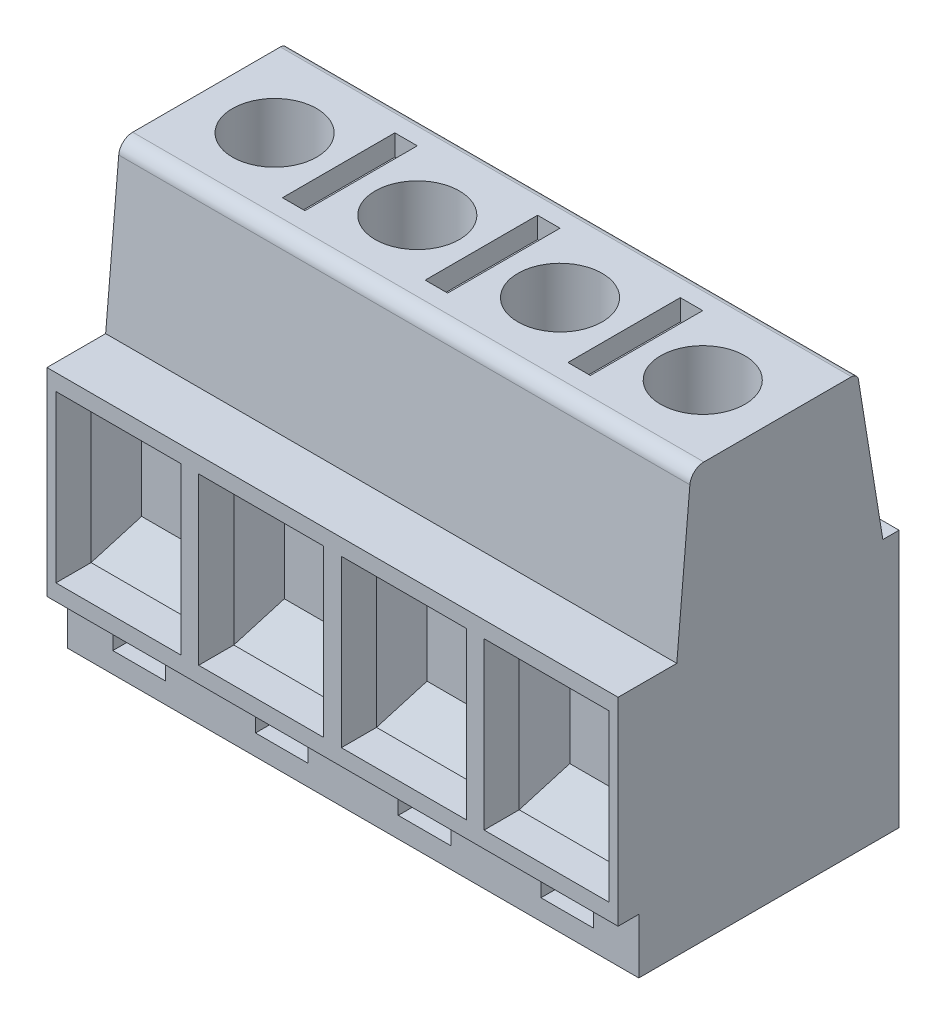
SolidWorks part; units mm, degrees
ref_plane "Front Plane" through (0, 0, 0) normal (0, 0, 1) x (1, 0, 0)
ref_plane "Top Plane" through (0, 0, 0) normal (0, 1, 0) x (1, 0, 0)
ref_plane "Right Plane" through (0, 0, 0) normal (1, 0, 0) x (0, 0, -1)
sketch "Sketch1" plane through (0, 0, 0) normal (1, 0, 0) x (0, 0, -1)
  line L0 (9.6447, 33.3244) -> (29.6447, 33.3244) construction
  line L1 (9.6692, 32.9692) -> (9.6692, 47.0868)
  line L2 (9.6692, 47.0868) -> (13.8475, 47.0868)
  line L3 (13.8475, 47.0868) -> (14.8593, 58.5419)
  line L4 (14.8593, 58.5419) -> (26.709, 58.5419)
  line L5 (26.709, 58.5419) -> (28.5149, 47.3865)
  line L6 (28.5149, 47.3865) -> (29.6692, 47.3865)
  line L7 (29.6692, 47.3865) -> (29.6692, 29.0419)
  line L8 (29.6692, 29.0419) -> (11.1423, 29.0419)
  line L9 (11.1423, 29.0419) -> (11.1423, 32.9692)
  line L10 (11.1423, 32.9692) -> (9.6692, 32.9692)
  line L11 (68.0457, 60.9618) -> (149.3457, 60.9618) construction
  line L12 (139.8559, 49.112) -> (148.7559, 49.112) construction
  line L13 (139.8559, 49.112) -> (139.8559, 37.312) construction
  line L14 (204.1416, 49.112) -> (206.6416, 49.112) construction
  line L15 (208.5587, 45.7504) -> (208.5587, 39.4578) construction
  line L16 (208.5587, 42.6041) -> (206.6416, 42.6041) construction
  line L17 (121.2763, 41.7533) -> (126.7736, 41.7533) construction
  line L18 (217.6919, 61.8593) -> (217.6919, 56.1569) construction
  line L19 (142.8406, 99.3741) -> (145.9297, 99.3741) construction
  line L20 (211.5813, 61.8593) -> (211.5813, 60.3558) construction
  line L21 (118.1896, 87.8673) -> (119.7969, 87.8673) construction
  line L22 (118.1896, 87.8673) -> (118.1896, 95.8627) construction
  line L23 (118.1896, 95.8627) -> (119.7969, 95.8627) construction
  line L24 (119.7969, 87.8673) -> (119.7969, 95.8627) construction
  line L25 (170.4098, 32.3653) -> (173.8098, 32.3653) construction
  line L26 (173.8098, 32.3653) -> (175.1098, 32.3653) construction
  line L27 (175.1098, 32.3653) -> (178.3098, 32.3653) construction
  line L28 (178.3098, 32.3653) -> (179.6098, 32.3653) construction
  line L29 (179.6098, 32.3653) -> (183.0098, 32.3653) construction
  line L30 (183.0098, 32.3653) -> (184.3098, 32.3653) construction
  line L31 (142.4541, 34.5696) -> (146.1866, 34.5696) construction
  line L32 (146.1866, 34.5696) -> (142.4541, 34.5696) construction
  line L33 (142.4541, 34.5696) -> (142.4541, 33.584) construction
  circle A0 centre (134.2519, 91.3377) radius 3.0186 construction
  dimension "D1" = 20
  dimension "D2" = 20
  dimension "D3" = 29.5
  dimension "D4" = 9.6692
  dimension "D5" = 11.1423
  dimension "D6" = 13.8475
  dimension "D7" = 14.8593
  dimension "D8" = 26.709
  dimension "D9" = 28.5149
  dimension "D10" = 29.0419
  dimension "D11" = 32.9692
  dimension "D12" = 33.3244
  dimension "D13" = 47.0868
  dimension "D14" = 47.3865
  dimension "D15" = 81.3
  dimension "D16" = 8.9
  dimension "D17" = 11.8
  dimension "D18" = 2.5
  dimension "D19" = 1.6073
  dimension "D20" = 7.9954
  dimension "D21" = 3.4
  dimension "D22" = 1.3
  dimension "D23" = 3.2
  dimension "D24" = 1.3
  dimension "D25" = 3.4
  dimension "D26" = 1.3
extrude "Boss-Extrude1" add sketch "Sketch1" along normal blind 10.16
sketch "Sketch2" plane through (0, 0, -9.6692) normal (0, 0, 1) x (1, 0, 0)
  line L0 (0, 47.0868) -> (0, 32.9692) construction
  line L1 (0.63, 34.128) -> (9.53, 34.128)
  line L2 (0.63, 34.128) -> (0.63, 45.928)
  line L3 (0.63, 45.928) -> (9.53, 45.928)
  line L4 (9.53, 34.128) -> (9.53, 45.928)
  line L5 (0.63, 34.128) -> (9.53, 45.928) construction
  line L6 (0.63, 45.928) -> (9.53, 34.128) construction
  line L7 (10.16, 47.0868) -> (0, 47.0868) construction
  point P0 (5.08, 40.028)
  point P5 (0, 0)
  point P8 (0, 40.028)
  point P9 (0, 0)
  point P12 (5.08, 47.0868)
  point P13 (9.3089, 45.6013)
  dimension "D1" = 8.9
  dimension "D2" = 11.8
extrude "Cut-Extrude1" cut sketch "Sketch2" against normal blind 2.5
sketch "Sketch3" plane through (0, 0, -12.1692) normal (0, 0, 1) x (1, 0, 0)
  line L4 (9.53, 34.128) -> (9.53, 45.928)
  line L5 (9.53, 45.928) -> (0.63, 45.928)
  line L6 (0.63, 45.928) -> (0.63, 34.128)
  line L7 (0.63, 34.128) -> (9.53, 34.128)
  line L8 (9.53, 34.128) -> (9.53, 45.928)
  line L9 (9.53, 45.928) -> (0.63, 45.928)
  line L10 (0.63, 45.928) -> (0.63, 34.128)
  line L11 (0.63, 34.128) -> (9.53, 34.128)
  dimension "D1" = 0
ref_plane "Plane1" through (0, 0, -14.0692) normal (0, 0, 1) x (1, 0, 0)
sketch "Sketch4" plane through (0, 0, -14.0692) normal (0, 0, 1) x (1, 0, 0)
  line L0 (9.53, 45.928) -> (0.63, 45.928) construction
  line L1 (2.33, 36.878) -> (7.83, 36.878)
  line L2 (2.33, 36.878) -> (2.33, 43.178)
  line L3 (2.33, 43.178) -> (7.83, 43.178)
  line L4 (7.83, 36.878) -> (7.83, 43.178)
  line L5 (2.33, 36.878) -> (7.83, 43.178) construction
  line L6 (2.33, 43.178) -> (7.83, 36.878) construction
  line L7 (0.63, 45.928) -> (0.63, 34.128) construction
  point P0 (5.08, 40.028)
  point P5 (0, 0)
  point P8 (5.08, 45.928)
  point P9 (0, 0)
  point P12 (0.63, 40.028)
  dimension "D1" = 6.3
  dimension "D2" = 5.5
loft "Cut-Loft1" cut profiles "Sketch3", "Sketch4" connector at (0.63, 45.928, -12.1692) connector at (2.33, 43.178, -14.0692)
sketch "Sketch5" plane through (0, 58.5419, 0) normal (0, 1, 0) x (1, 0, 0)
  line L0 (10.16, 26.709) -> (10.16, 14.8593) construction
  line L1 (10.16, 29.6692) -> (0, 29.6692) construction
  circle A0 centre (5.08, 20.7842) radius 3
  point P2 (0, 0)
  point P5 (10.16, 20.7842)
  point P6 (0, 0)
  point P9 (5.08, 29.6692)
  dimension "D1" = 6
extrude "Cut-Extrude2" cut sketch "Sketch5" against normal blind 5.7
sketch "Sketch7" plane through (0, 29.0419, 0) normal (0, -1, 0) x (1, 0, 0)
  line L0 (10.16, -11.1423) -> (0, -11.1423) construction
  line L1 (4.43, -27.5692) -> (5.73, -27.5692)
  line L2 (4.43, -27.5692) -> (4.43, -26.7692)
  line L3 (4.43, -26.7692) -> (5.73, -26.7692)
  line L4 (5.73, -27.5692) -> (5.73, -26.7692)
  line L5 (4.43, -27.5692) -> (5.73, -26.7692) construction
  line L6 (4.43, -26.7692) -> (5.73, -27.5692) construction
  line L7 (4.43, -17.4092) -> (5.73, -17.4092)
  line L8 (4.43, -17.4092) -> (4.43, -16.6092)
  line L9 (4.43, -16.6092) -> (5.73, -16.6092)
  line L10 (5.73, -17.4092) -> (5.73, -16.6092)
  line L11 (4.43, -17.4092) -> (5.73, -16.6092) construction
  line L12 (4.43, -16.6092) -> (5.73, -17.4092) construction
  line L13 (10.16, -29.6692) -> (0, -29.6692) construction
  point P0 (5.08, -27.1692)
  point P5 (5.08, -17.0092)
  point P10 (0, 0)
  point P13 (5.08, -11.1423)
  dimension "D1" = 1.3
  dimension "D2" = 0.8
  dimension "D3" = 2.5
  dimension "D4" = 10.16
extrude "Boss-Extrude2" add sketch "Sketch7" along normal blind 4.5
sketch "Sketch8" plane through (0, 0, -16.6092) normal (0, 0, 1) x (1, 0, 0)
  line L0 (4.43, 24.5419) -> (4.43, 29.0419) construction
  line L1 (5.73, 24.5419) -> (5.73, 29.0419) construction
  line L2 (5.73, 24.5419) -> (4.43, 24.5419) construction
  arc A0 (4.43, 25.1919) -> (5.73, 25.1919) centre (5.08, 25.1919) ccw
  point P3 (5.08, 24.5419)
extrude "Cut-Extrude5" cut sketch "Sketch8" against normal through all flip side to cut
ref_plane "Plane2" through (0, 38.5279, -38.5279) normal (0, 0.7071, -0.7071) x (-1, 0, 0)
sketch "Sketch10" plane through (0, 38.5279, -38.5279) normal (0, 0.7071, -0.7071) x (-1, 0, 0)
  line L0 (-10.16, 12.528) -> (0, 12.528) construction
  circle A0 centre (-5.08, 12.528) radius 1.5
  dimension "D1" = 3
extrude "Cut-Extrude6" cut sketch "Sketch10" against normal blind 4.5 contours A0
sketch "Sketch13" plane through (0, 0, -11.1423) normal (0, 0, 1) x (1, 0, 0)
  line L0 (10.16, 32.9692) -> (10.16, 29.0419) construction
  line L1 (3.205, 30.5055) -> (6.955, 30.5055)
  line L2 (3.205, 30.5055) -> (3.205, 31.5055)
  line L3 (3.205, 31.5055) -> (6.955, 31.5055)
  line L4 (6.955, 30.5055) -> (6.955, 31.5055)
  line L5 (3.205, 30.5055) -> (6.955, 31.5055) construction
  line L6 (3.205, 31.5055) -> (6.955, 30.5055) construction
  line L7 (10.16, 32.9692) -> (0, 32.9692) construction
  point P0 (5.08, 31.0055)
  point P5 (0, 0)
  point P8 (10.16, 31.0055)
  point P9 (0, 0)
  point P12 (5.08, 32.9692)
  dimension "D1" = 3.75
  dimension "D2" = 1
extrude "Cut-Extrude8" cut sketch "Sketch13" against normal blind 3
fillet "Fillet3" radius 0.5 1 edges at (5.08, 58.5419, -26.709) type face fillet first side face at (5.08, 58.5419, -17.7842) second side face at (5.08, 51.2437, -27.8905)
fillet "Fillet4" radius 1 1 edges at (5.08, 58.5419, -14.8593) type face fillet first side face at (5.08, 58.5419, -17.7842) second side face at (5.08, 52.8143, -14.3534)
sketch "Sketch12" plane through (0, 29.0419, 0) normal (0, -1, 0) x (1, 0, 0)
  line L1 (-0.65, -15.8423) -> (0.65, -15.8423)
  line L2 (-0.65, -15.8423) -> (-0.65, -14.5423)
  line L3 (-0.65, -14.5423) -> (0.65, -14.5423)
  line L4 (0.65, -15.8423) -> (0.65, -14.5423)
  line L5 (-0.65, -15.8423) -> (0.65, -14.5423) construction
  line L6 (-0.65, -14.5423) -> (0.65, -15.8423) construction
  line L8 (-0.65, -20.3423) -> (0.65, -20.3423)
  line L9 (-0.65, -20.3423) -> (-0.65, -19.0423)
  line L10 (-0.65, -19.0423) -> (0.65, -19.0423)
  line L11 (0.65, -20.3423) -> (0.65, -19.0423)
  line L12 (-0.65, -20.3423) -> (0.65, -19.0423) construction
  line L13 (-0.65, -19.0423) -> (0.65, -20.3423) construction
  line L14 (-0.65, -25.0423) -> (0.65, -25.0423)
  line L15 (-0.65, -25.0423) -> (-0.65, -23.7423)
  line L16 (-0.65, -23.7423) -> (0.65, -23.7423)
  line L17 (0.65, -25.0423) -> (0.65, -23.7423)
  line L18 (-0.65, -25.0423) -> (0.65, -23.7423) construction
  line L19 (-0.65, -23.7423) -> (0.65, -25.0423) construction
  line L20 (10.16, -11.1423) -> (0, -11.1423) construction
  line L21 (0, -11.1423) -> (0, -29.6692) construction
  point P0 (0, -15.1923)
  point P5 (0, 0)
  point P6 (0, -15.1923)
  point P7 (0, -19.6923)
  point P12 (0, -24.3923)
  point P21 (0, 0)
  point P22 (0, 0)
  point P23 (0, -15.1923)
  point P24 (0, -19.6923)
  point P25 (0, -24.3923)
  dimension "D1" = 3.4
  dimension "D2" = 1.3
  dimension "D3" = 3.2
  dimension "D4" = 3.4
  dimension "D5" = 1.3
extrude "Boss-Extrude3" add sketch "Sketch12" along normal blind 0.5 separate body
sketch "Sketch14" plane through (10.16, 0, 0) normal (1, 0, 0) x (0, 0, -1)
  line L10 (26.2835, 58.5419) -> (15.7749, 58.5419)
  line L11 (14.7788, 57.6298) -> (13.8475, 47.0868)
  line L12 (13.8475, 47.0868) -> (9.6692, 47.0868)
  line L13 (9.6692, 47.0868) -> (9.6692, 32.9692)
  line L14 (9.6692, 32.9692) -> (11.1423, 32.9692)
  line L15 (11.1423, 32.9692) -> (11.1423, 29.0419)
  line L16 (11.1423, 29.0419) -> (29.6692, 29.0419)
  line L17 (29.6692, 29.0419) -> (29.6692, 47.3865)
  line L18 (29.6692, 47.3865) -> (28.5149, 47.3865)
  line L19 (28.5149, 47.3865) -> (26.777, 58.1218)
  line L21 (14.7788, 57.6298) -> (13.8475, 47.0868)
  line L22 (13.8475, 47.0868) -> (9.6692, 47.0868)
  line L23 (9.6692, 47.0868) -> (9.6692, 32.9692)
  line L24 (9.6692, 32.9692) -> (11.1423, 32.9692)
  line L25 (11.1423, 32.9692) -> (11.1423, 29.0419)
  line L26 (11.1423, 29.0419) -> (29.6692, 29.0419)
  line L27 (29.6692, 29.0419) -> (29.6692, 47.3865)
  line L28 (29.6692, 47.3865) -> (28.5149, 47.3865)
  line L29 (28.5149, 47.3865) -> (26.777, 58.1218)
  line L31 (26.2835, 58.5419) -> (15.7749, 58.5419)
  arc A3 (26.777, 58.1218) -> (26.2835, 58.5419) centre (26.2835, 58.0419) ccw
  arc A6 (26.777, 58.1218) -> (26.2835, 58.5419) centre (26.2835, 58.0419) ccw
  arc A8 (15.7749, 58.5419) -> (14.7788, 57.6298) centre (15.7749, 57.5419) ccw
  arc A9 (15.7749, 58.5419) -> (14.7788, 57.6298) centre (15.7749, 57.5419) ccw
  dimension "D1" = 0
extrude "Boss-Extrude4" add sketch "Sketch14" along normal blind 0.01
ref_plane "Plane3" through (0, 0, 0) normal (-1, 0, 0) x (0, 0, 1)
pattern_linear "LPattern8" count 4 spacing 10.16 along (-1, 0, 0) of "Boss-Extrude1", "Cut-Extrude1", "Cut-Loft1", "Cut-Extrude2", "Boss-Extrude2", "Cut-Extrude5", "Cut-Extrude6", "Cut-Extrude8", "Fillet3", "Fillet4"
sketch "Sketch11" plane through (0, 58.5419, 0) normal (0, 1, 0) x (1, 0, 0)
  line L1 (-0.8, 17.0641) -> (0.8, 17.0641)
  line L2 (-0.8, 17.0641) -> (-0.8, 25.0641)
  line L3 (-0.8, 25.0641) -> (0.8, 25.0641)
  line L4 (0.8, 17.0641) -> (0.8, 25.0641)
  line L5 (-0.8, 17.0641) -> (0.8, 25.0641) construction
  line L6 (-0.8, 25.0641) -> (0.8, 17.0641) construction
  line L8 (0, 55) -> (0, -55) construction
  point P0 (0, 21.0641)
  point P5 (1.8522, 20.6032)
  point P6 (1.6707, 20.773)
  point P7 (0, 0)
  point P8 (0, 0)
  point P12 (0, 0)
  point P13 (0.3317, 21.0641)
  point P16 (0, 0)
  dimension "D1" = 1.6
  dimension "D2" = 8
extrude "Cut-Extrude7" cut sketch "Sketch11" against normal blind 1.5
pattern_linear "LPattern9" count 3 spacing 10.16 along (-1, 0, 0) of "Boss-Extrude3", "Cut-Extrude7"
sketch "Sketch16" plane through (-30.48, 0, 0) normal (-1, 0, 0) x (0, 0, 1)
  line L10 (-13.8475, 47.0868) -> (-14.7788, 57.6298)
  line L11 (-15.7749, 58.5419) -> (-26.2835, 58.5419)
  line L12 (-26.777, 58.1218) -> (-28.5149, 47.3865)
  line L13 (-28.5149, 47.3865) -> (-29.6692, 47.3865)
  line L14 (-29.6692, 47.3865) -> (-29.6692, 29.0419)
  line L15 (-29.6692, 29.0419) -> (-11.1423, 29.0419)
  line L16 (-11.1423, 29.0419) -> (-11.1423, 32.9692)
  line L17 (-11.1423, 32.9692) -> (-9.6692, 32.9692)
  line L18 (-9.6692, 32.9692) -> (-9.6692, 47.0868)
  line L19 (-9.6692, 47.0868) -> (-13.8475, 47.0868)
  line L52 (-13.8475, 47.0868) -> (-14.7788, 57.6298)
  line L53 (-15.7749, 58.5419) -> (-26.2835, 58.5419)
  line L54 (-26.777, 58.1218) -> (-28.5149, 47.3865)
  line L55 (-28.5149, 47.3865) -> (-29.6692, 47.3865)
  line L56 (-29.6692, 47.3865) -> (-29.6692, 29.0419)
  line L57 (-29.6692, 29.0419) -> (-11.1423, 29.0419)
  line L58 (-11.1423, 29.0419) -> (-11.1423, 32.9692)
  line L59 (-11.1423, 32.9692) -> (-9.6692, 32.9692)
  line L60 (-9.6692, 32.9692) -> (-9.6692, 47.0868)
  line L61 (-9.6692, 47.0868) -> (-13.8475, 47.0868)
  arc A2 (-14.7788, 57.6298) -> (-15.7749, 58.5419) centre (-15.7749, 57.5419) ccw
  arc A8 (-26.2835, 58.5419) -> (-26.777, 58.1218) centre (-26.2835, 58.0419) ccw
  arc A12 (-14.7788, 57.6298) -> (-15.7749, 58.5419) centre (-15.7749, 57.5419) ccw
  arc A13 (-26.2835, 58.5419) -> (-26.777, 58.1218) centre (-26.2835, 58.0419) ccw
  dimension "D1" = 0
extrude "Boss-Extrude6" add sketch "Sketch16" along normal blind 0.01
